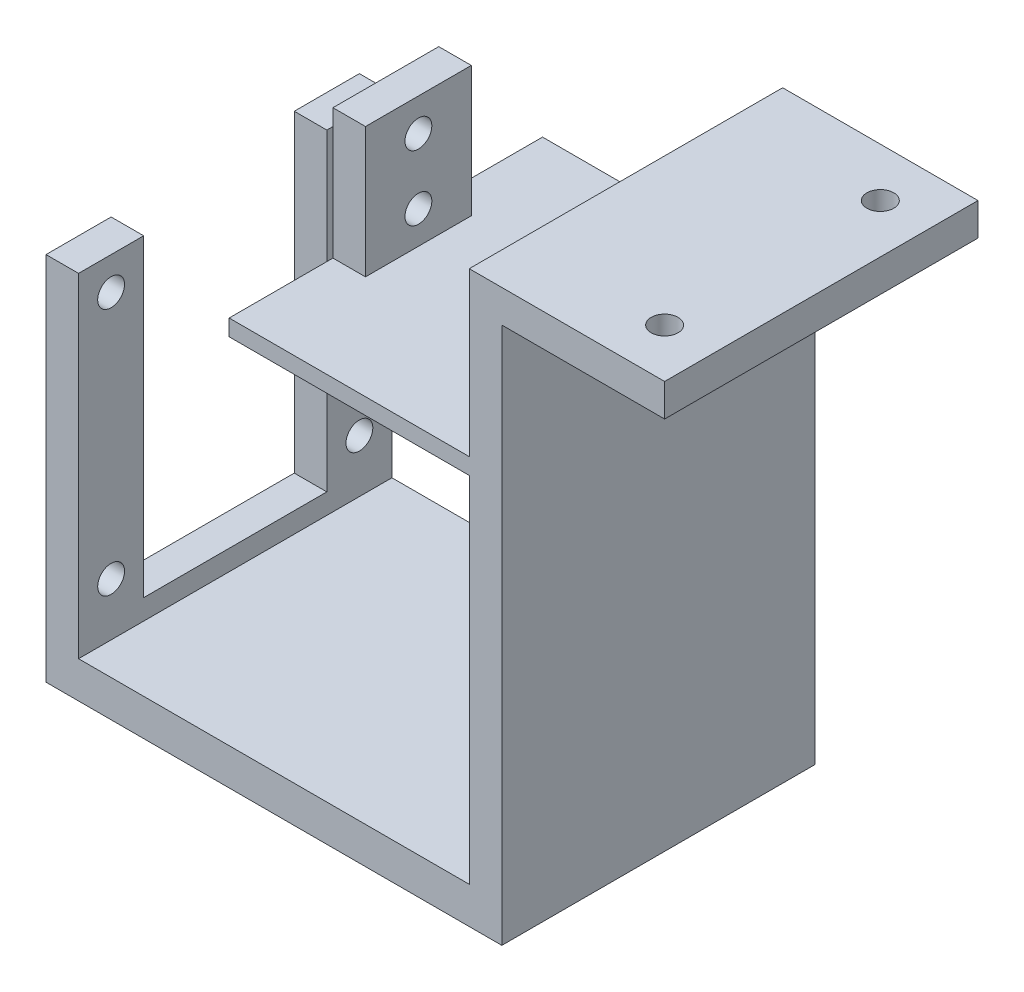
SolidWorks part; units mm, degrees
ref_plane "Front Plane" through (0, 0, 0) normal (0, 0, 1) x (1, 0, 0)
ref_plane "Top Plane" through (0, 0, 0) normal (0, 1, 0) x (1, 0, 0)
ref_plane "Right Plane" through (0, 0, 0) normal (1, 0, 0) x (0, 0, -1)
sketch "Sketch1" plane through (0, 0, 0) normal (1, 0, 0) x (0, 0, -1)
  line L1 (0, 0) -> (13, 0)
  line L2 (0, 0) -> (0, -16)
  line L3 (0, -16) -> (13, -16)
  line L4 (13, 0) -> (13, -16)
  dimension "D1" = 13
  dimension "D2" = 16
extrude "Boss-Extrude1" add sketch "Sketch1" along normal blind 4
sketch "Sketch2" plane through (4, 0, 0) normal (1, 0, 0) x (0, 0, -1)
  line L0 (13, 0) -> (0, 0) construction
  line L1 (0, -16) -> (13, -16) construction
  line L2 (13, -16) -> (13, 0) construction
  line L3 (0, 0) -> (0, -16) construction
  circle A0 centre (6.5, -4) radius 1.65
  circle A1 centre (6.5, -12) radius 1.65
  dimension "D1" = 3.3
  dimension "D2" = 3.3
  dimension "D3" = 4
  dimension "D4" = 4
  dimension "D5" = 6.5
  dimension "D6" = 6.5
extrude "Cut-Extrude1" cut sketch "Sketch2" against normal blind 10
sketch "Sketch3" plane through (0, -16, 0) normal (0, -1, 0) x (1, 0, 0)
  line L1 (4, 0) -> (0, 0)
  line L2 (4, 0) -> (4, -13)
  line L3 (4, -13) -> (0, -13)
  line L4 (0, 0) -> (0, -13)
extrude "Boss-Extrude2" add sketch "Sketch3" along normal blind 4
sketch "Sketch4" plane through (4, 0, 0) normal (1, 0, 0) x (0, 0, -1)
  line L0 (13, -20) -> (13, 0) construction
  line L1 (0, -20) -> (13, -20)
  line L2 (0, -20) -> (0, -16)
  line L3 (0, -16) -> (13, -16)
  line L4 (13, -20) -> (13, -16)
  dimension "D1" = 4
extrude "Boss-Extrude3" add sketch "Sketch4" along normal blind 60
sketch "Sketch6" plane through (0, -16, 0) normal (0, 1, 0) x (1, 0, 0)
  line L0 (64, 0) -> (4, 0) construction
  line L1 (64, 13) -> (60, 13)
  line L2 (64, 13) -> (64, -21)
  line L3 (64, -21) -> (60, -21)
  line L4 (60, 13) -> (60, -21)
  line L7 (64, 13) -> (60, 13)
  line L8 (64, 13) -> (64, 34)
  line L9 (64, 34) -> (60, 34)
  line L10 (60, 13) -> (60, 34)
  line M2 (4, 0) -> (64, 0)
  line M3 (64, 0) -> (64, 13)
  line M4 (64, 13) -> (4, 13)
  dimension "D1" = 4
  dimension "D2" = 21
  dimension "D3" = 21
extrude "Boss-Extrude4" add sketch "Sketch6" along normal blind 28 contours L4 L3 L2 M2 | L10 L8 L9 M4 | L4 M4 M2 M3 region at (62, -16, -6.5) region at (62, -16, -23.5) region at (62, -16, 10.5)
sketch "Sketch12" plane through (0, 0, -34) normal (0, 0, -1) x (-1, 0, 0)
  line L1 (-60, -16) -> (-64, -16)
  line L2 (-60, -16) -> (-60, 12)
  line L3 (-60, 12) -> (-64, 12)
  line L4 (-64, -16) -> (-64, 12)
extrude "Boss-Extrude8" add sketch "Sketch12" along normal blind 1.65
sketch "Sketch13" plane through (0, 0, 21) normal (0, 0, 1) x (1, 0, 0)
  line L1 (60, 12) -> (64, 12)
  line L2 (60, 12) -> (60, -16)
  line L3 (60, -16) -> (64, -16)
  line L4 (64, 12) -> (64, -16)
extrude "Boss-Extrude9" add sketch "Sketch13" along normal blind 1.65
sketch "Sketch14" plane through (0, 12, 0) normal (0, 1, 0) x (1, 0, 0)
  line L0 (64, 35.65) -> (64, -22.65) construction
  line L1 (64, 24.35) -> (60, 24.35)
  line L2 (64, 24.35) -> (64, -11.5284)
  line L3 (64, -11.5284) -> (60, -11.5284)
  line L4 (60, 24.35) -> (60, -11.5284)
  line L5 (60, 35.65) -> (60, -22.65) construction
  line L6 (64, -22.65) -> (60, -22.65) construction
  line L7 (60, 35.65) -> (64, 35.65) construction
  point P10 (62, -22.65)
  dimension "D1" = 11.3
  dimension "D2" = 11.3
extrude "Cut-Extrude5" cut sketch "Sketch14" against normal blind 24
sketch "Sketch15" plane through (64, 0, 0) normal (1, 0, 0) x (0, 0, -1)
  line L0 (-11.5284, 12) -> (-22.65, 12) construction
  line L1 (35.65, 12) -> (24.35, 12) construction
  line L2 (-22.65, -16) -> (-22.65, 12) construction
  line L3 (35.65, 12) -> (35.65, -16) construction
  circle A0 centre (-17, -11.5) radius 1.65
  circle A1 centre (30, -11.5) radius 1.65
  dimension "D1" = 3.3
  dimension "D2" = 3.3
  dimension "D3" = 23.5
  dimension "D4" = 23.5
  dimension "D5" = 5.65
  dimension "D6" = 5.65
extrude "Cut-Extrude6" cut sketch "Sketch15" against normal blind 24
sketch "Sketch16" plane through (0, 12, 0) normal (0, 1, 0) x (1, 0, 0)
  line L1 (60, -22.65) -> (64, -22.65)
  line L2 (60, -22.65) -> (60, -11.5284)
  line L3 (60, -11.5284) -> (64, -11.5284)
  line L4 (64, -22.65) -> (64, -11.5284)
  line L5 (60, 24.35) -> (64, 24.35)
  line L6 (60, 24.35) -> (60, 35.65)
  line L7 (60, 35.65) -> (64, 35.65)
  line L8 (64, 24.35) -> (64, 35.65)
extrude "Boss-Extrude10" add sketch "Sketch16" along normal blind 29.15
sketch "Sketch17" plane through (64, 0, 0) normal (1, 0, 0) x (0, 0, -1)
  line L0 (-22.65, -16) -> (-22.65, 41.15) construction
  line L1 (35.65, 41.15) -> (35.65, -16) construction
  line L2 (-22.65, 41.15) -> (-11.5284, 41.15) construction
  line L3 (24.35, 41.15) -> (35.65, 41.15) construction
  circle A0 centre (-17, 35.5) radius 1.65
  circle A1 centre (30, 35.5) radius 1.65
  dimension "D1" = 3.3
  dimension "D2" = 3.3
  dimension "D4" = 5.65
  dimension "D3" = 5.65
  dimension "D5" = 5.65
  dimension "D6" = 5.65
extrude "Cut-Extrude8" cut sketch "Sketch17" against normal blind 29.15
sketch "Sketch18" plane through (64, 0, 0) normal (1, 0, 0) x (0, 0, -1)
  line L1 (-22.65, -16) -> (13, -16)
  line L2 (-22.65, -16) -> (-22.65, -20)
  line L3 (-22.65, -20) -> (13, -20)
  line L4 (13, -16) -> (13, -20)
  line L5 (0, -20) -> (35.65, -20)
  line L6 (0, -20) -> (0, -16)
  line L7 (0, -16) -> (35.65, -16)
  line L8 (35.65, -20) -> (35.65, -16)
  line M9 (-22.65, -16) -> (0, -16)
  line M10 (0, -16) -> (0, -20)
  line M11 (0, -20) -> (13, -20)
  line M12 (13, -20) -> (13, -16)
  line M13 (13, -16) -> (35.65, -16)
extrude "Boss-Extrude11" add sketch "Sketch18" against normal blind 4 contours L2 L3 M10 M9 | L5 L8 M13 M12 | L1 M10 M11 M12 region at (64, -18, 11.325) region at (64, -18, -6.5) region at (64, -18, -24.325)
sketch "Sketch19" plane through (0, 0, -13) normal (0, 0, -1) x (-1, 0, 0)
  line L1 (0, -20) -> (-4, -20)
  line L2 (0, -20) -> (0, 0)
  line L3 (0, 0) -> (-4, 0)
  line L4 (-4, -20) -> (-4, 0)
extrude "Boss-Extrude12" add sketch "Sketch19" along normal blind 40
sketch "Sketch20" plane through (0, 0, 0) normal (-1, 0, 0) x (0, 0, 1)
  line L0 (-53, 0) -> (0, 0) construction
  line L1 (-53, -20) -> (-53, 0) construction
  circle A0 centre (-46.5, -4) radius 1.65
  circle A1 centre (-46.5, -12) radius 1.65
  dimension "D1" = 3.3
  dimension "D2" = 3.3
  dimension "D3" = 4
  dimension "D4" = 8
  dimension "D5" = 6.5
  dimension "D6" = 6.5
extrude "Cut-Extrude9" cut sketch "Sketch20" against normal blind 40
sketch "Sketch21" plane through (0, -16, 0) normal (0, 1, 0) x (1, 0, 0)
  line L0 (4, 53) -> (4, 13) construction
  line L1 (28, 21.75) -> (24, 21.75)
  line L2 (28, 21.75) -> (28, -8.75)
  line L3 (28, -8.75) -> (24, -8.75)
  line L4 (24, 21.75) -> (24, -8.75)
  line L5 (60, 13) -> (4, 13) construction
  line L6 (60, 0) -> (4, 0) construction
  dimension "D1" = 20
  dimension "D2" = 4
  dimension "D3" = 8.75
  dimension "D4" = 8.75
extrude "Boss-Extrude13" add sketch "Sketch21" along normal blind 38.5
sketch "Sketch23" plane through (0, 22.5, 0) normal (0, 1, 0) x (1, 0, 0)
  line L1 (24, 21.75) -> (28, 21.75)
  line L2 (24, 21.75) -> (24, 25.75)
  line L3 (24, 25.75) -> (28, 25.75)
  line L4 (28, 21.75) -> (28, 25.75)
  line L6 (24, 21.75) -> (24, -8.75) construction
  line L7 (28, -8.75) -> (28, 21.75) construction
  line L8 (24, -8.75) -> (28, -8.75)
  line L9 (24, -8.75) -> (24, -12.75)
  line L10 (24, -12.75) -> (28, -12.75)
  line L11 (28, -8.75) -> (28, -12.75)
  dimension "D1" = 4
  dimension "D2" = 4
  dimension "D3" = 4
  dimension "D4" = 0
extrude "Boss-Extrude14" add sketch "Sketch23" against normal blind 38.5
sketch "Sketch24" plane through (0, 22.5, 0) normal (0, 1, 0) x (1, 0, 0)
  line L1 (28, 25.75) -> (24, 25.75)
  line L2 (28, 25.75) -> (28, -12.75)
  line L3 (28, -12.75) -> (24, -12.75)
  line L4 (24, 25.75) -> (24, -12.75)
extrude "Boss-Extrude15" add sketch "Sketch24" along normal blind 3
sketch "Sketch25" plane through (28, 0, 0) normal (1, 0, 0) x (0, 0, -1)
  line L0 (25.75, -16) -> (25.75, 25.5) construction
  line L1 (25.75, -13) -> (-12.75, -13)
  line L2 (25.75, -13) -> (25.75, -20)
  line L3 (25.75, -20) -> (-12.75, -20)
  line L4 (-12.75, -13) -> (-12.75, -20)
  line L5 (13, -16) -> (25.75, -16) construction
  line L6 (-12.75, -16) -> (0, -16) construction
  line L7 (-12.75, -16) -> (-12.75, 25.5) construction
  dimension "D1" = 3
  dimension "D2" = 4
  dimension "D3" = 0
sketch "Sketch27" plane through (0, -20, 0) normal (0, -1, 0) x (1, 0, 0)
  line L1 (64, 22.65) -> (60, 22.65)
  line L2 (64, 22.65) -> (64, -35.65)
  line L3 (64, -35.65) -> (60, -35.65)
  line L4 (60, 22.65) -> (60, -35.65)
extrude "Cut-Extrude10" cut sketch "Sketch27" against normal blind 100
sketch "Sketch29" plane through (28, 0, 0) normal (1, 0, 0) x (0, 0, -1)
  line L2 (-12.75, -13) -> (25.75, -13)
  line L3 (-12.75, -13) -> (-12.75, -20)
  line L4 (-12.75, -20) -> (25.75, -20)
  line L5 (25.75, -13) -> (25.75, -20)
extrude "Boss-Extrude16" add sketch "Sketch29" along normal blind 40 and the other way blind 28
sketch "Sketch30" plane through (24, 0, 0) normal (-1, 0, 0) x (0, 0, 1)
  line L0 (12.75, -13) -> (12.75, 25.5) construction
  line L1 (-25.75, 25.5) -> (12.75, 25.5) construction
  line L2 (-25.75, -13) -> (12.75, -13) construction
  line L3 (-25.75, -13) -> (-25.75, 25.5) construction
  circle A0 centre (8.75, 21.5) radius 1.65
  circle A1 centre (8.75, -9) radius 1.65
  circle A2 centre (-21.75, 21.5) radius 1.65
  circle A3 centre (-21.75, -9) radius 1.65
  dimension "D1" = 3.3
  dimension "D4" = 3.3
  dimension "D7" = 3.3
  dimension "D12" = 3.3
  dimension "D2" = 4
  dimension "D3" = 4
  dimension "D5" = 4
  dimension "D6" = 4
  dimension "D8" = 4
  dimension "D9" = 4
  dimension "D10" = 4
  dimension "D11" = 4
extrude "Cut-Extrude11" cut sketch "Sketch30" against normal blind 40
sketch "Sketch31" plane through (0, 25.5, 0) normal (0, 1, 0) x (1, 0, 0)
  line L0 (28, -12.75) -> (28, 25.75) construction
  line L1 (28, 17.75) -> (24, 17.75)
  line L2 (28, 17.75) -> (28, -4.75)
  line L3 (28, -4.75) -> (24, -4.75)
  line L4 (24, 17.75) -> (24, -4.75)
  line L5 (24, 25.75) -> (24, -12.75) construction
  line L6 (24, -12.75) -> (28, -12.75) construction
  dimension "D1" = 8
  dimension "D2" = 8
extrude "Cut-Extrude12" cut sketch "Sketch31" against normal blind 38.5
sketch "Sketch32" plane through (68, 0, 0) normal (1, 0, 0) x (0, 0, -1)
  line L0 (25.75, -20) -> (25.75, -13) construction
  line L1 (-12.75, -13) -> (25.75, -13)
  line L2 (-12.75, -13) -> (-12.75, -15.5)
  line L3 (-12.75, -15.5) -> (25.75, -15.5)
  line L4 (25.75, -13) -> (25.75, -15.5)
  dimension "D1" = 2.5
extrude "Cut-Extrude13" cut sketch "Sketch32" against normal blind 40
sketch "Sketch33" plane through (0, 25.5, 0) normal (0, 1, 0) x (1, 0, 0)
  line L1 (24, -12.75) -> (28, -12.75)
  line L2 (24, -12.75) -> (24, -4.75)
  line L3 (24, -4.75) -> (28, -4.75)
  line L4 (28, -12.75) -> (28, -4.75)
  line L5 (24, 17.75) -> (28, 17.75)
  line L6 (24, 17.75) -> (24, 25.75)
  line L7 (24, 25.75) -> (28, 25.75)
  line L8 (28, 17.75) -> (28, 25.75)
extrude "Boss-Extrude17" add sketch "Sketch33" against normal blind 8
sketch "Sketch34" plane through (28, 0, 0) normal (1, 0, 0) x (0, 0, -1)
  line L0 (-12.75, 25.5) -> (-4.75, 25.5) construction
  line L1 (-12.75, -15.5) -> (-12.75, 25.5) construction
  line L2 (25.75, -15.5) -> (25.75, 25.5) construction
  line L3 (17.75, 25.5) -> (25.75, 25.5) construction
  circle A0 centre (-8.75, 21.5) radius 1.65
  circle A1 centre (21.75, 21.5) radius 1.65
  dimension "D1" = 3.3
  dimension "D2" = 3.3
  dimension "D3" = 4
  dimension "D4" = 4
  dimension "D5" = 4
  dimension "D6" = 4
extrude "Cut-Extrude14" cut sketch "Sketch34" against normal blind 8
sketch "Sketch35" plane through (0, -13, 0) normal (0, 1, 0) x (1, 0, 0)
  line L0 (0, -12.75) -> (24, -12.75) construction
  line L1 (10, -12.75) -> (14, -12.75)
  line L2 (10, -12.75) -> (10, 30.75)
  line L3 (10, 30.75) -> (14, 30.75)
  line L4 (14, -12.75) -> (14, 30.75)
  line L5 (24, 25.75) -> (24, 17.75) construction
  line L6 (4, 25.75) -> (24, 25.75) construction
  dimension "D1" = 10
  dimension "D2" = 4
  dimension "D3" = 5
extrude "Boss-Extrude18" add sketch "Sketch35" along normal blind 13
sketch "Sketch36" plane through (0, -20, 0) normal (0, -1, 0) x (1, 0, 0)
  line L1 (0, 12.75) -> (68, 12.75) construction
  line L2 (0, 12.75) -> (10, 12.75)
  line L3 (0, 12.75) -> (0, -67.25)
  line L4 (0, -67.25) -> (10, -67.25)
  line L5 (10, 12.75) -> (10, -67.25)
  line L6 (4, -53) -> (4, -25.75) construction
  dimension "D1" = 10
  dimension "D2" = 80
  dimension "D3" = 4
extrude "Cut-Extrude15" cut sketch "Sketch36" against normal up to vertex (45.5 mm away) up to point (24, 25.5, -25.75)
sketch "Sketch37" plane through (10, 0, 0) normal (-1, 0, 0) x (0, 0, 1)
  line L1 (-30.75, -13) -> (-25.75, -13)
  line L2 (-30.75, -13) -> (-30.75, -20)
  line L3 (-30.75, -20) -> (-25.75, -20)
  line L4 (-25.75, -13) -> (-25.75, -20)
extrude "Boss-Extrude19" add sketch "Sketch37" against normal blind 4
sketch "Sketch41" plane through (14, 0, 0) normal (1, 0, 0) x (0, 0, -1)
  line L1 (25.75, -20) -> (38.75, -20)
  line L2 (25.75, -20) -> (25.75, 0)
  line L3 (25.75, 0) -> (38.75, 0)
  line L4 (38.75, -20) -> (38.75, 0)
  dimension "D1" = 13
  dimension "D2" = 20
extrude "Boss-Extrude20" add sketch "Sketch41" against normal blind 4
sketch "Sketch42" plane through (10, 0, 0) normal (-1, 0, 0) x (0, 0, 1)
  line L0 (-38.75, 0) -> (12.75, 0) construction
  line L1 (-38.75, -20) -> (-38.75, 0) construction
  circle A0 centre (-32.25, -4) radius 1.65
  circle A1 centre (-32.25, -12) radius 1.65
  dimension "D1" = 3.3
  dimension "D2" = 3.3
  dimension "D3" = 4
  dimension "D4" = 6.5
  dimension "D5" = 8
  dimension "D6" = 6.5
extrude "Cut-Extrude18" cut sketch "Sketch42" against normal blind 4
sketch "Sketch43" plane through (0, 0, 0) normal (0, 1, 0) x (1, 0, 0)
  line L0 (10, 38.75) -> (10, -12.75) construction
  line L1 (14, -12.75) -> (10, -12.75)
  line L2 (14, -12.75) -> (14, 25.75)
  line L3 (14, 25.75) -> (10, 25.75)
  line L4 (10, -12.75) -> (10, 25.75)
  line L5 (10, 38.75) -> (14, 38.75) construction
  dimension "D1" = 13
extrude "Cut-Extrude19" cut sketch "Sketch43" against normal blind 10
sketch "Sketch44" plane through (28, 0, 0) normal (1, 0, 0) x (0, 0, -1)
  line L0 (-4.75, -13) -> (-4.75, 25.5) construction
  line L1 (-12.75, -15.5) -> (-4.75, -15.5)
  line L2 (-12.75, -15.5) -> (-12.75, -6.5)
  line L3 (-12.75, -6.5) -> (-4.75, -6.5)
  line L4 (-4.75, -15.5) -> (-4.75, -6.5)
  line L5 (17.75, -13) -> (17.75, 25.5) construction
  line L6 (25.75, -15.5) -> (17.75, -15.5)
  line L7 (25.75, -15.5) -> (25.75, -6.5)
  line L8 (25.75, -6.5) -> (17.75, -6.5)
  line L9 (17.75, -15.5) -> (17.75, -6.5)
  dimension "D1" = 9
  dimension "D2" = 9
extrude "Boss-Extrude21" add sketch "Sketch44" against normal blind 4
sketch "Sketch45" plane through (24, 0, 0) normal (-1, 0, 0) x (0, 0, 1)
  line L0 (4.75, -13) -> (12.75, -13) construction
  line L1 (-25.75, -13) -> (-17.75, -13) construction
  line L2 (-25.75, -13) -> (-25.75, 25.5) construction
  line L3 (12.75, -13) -> (12.75, 25.5) construction
  circle A0 centre (-21.75, -7) radius 1.65
  circle A1 centre (8.75, -7) radius 1.65
  dimension "D1" = 3.3
  dimension "D2" = 3.3
  dimension "D3" = 6
  dimension "D4" = 6
  dimension "D5" = 4
  dimension "D6" = 4
extrude "Cut-Extrude20" cut sketch "Sketch45" against normal blind 4
sketch "Sketch46" plane through (0, -15.5, 0) normal (0, 1, 0) x (1, 0, 0)
  line L0 (68, -12.75) -> (68, 25.75) construction
  line L1 (64, 18.2859) -> (67, 20.0179)
  line L2 (67, 20.0179) -> (67, 23.4821)
  line L3 (67, 23.4821) -> (64, 25.2141)
  line L4 (64, 25.2141) -> (61, 23.4821)
  line L5 (61, 23.4821) -> (61, 20.0179)
  line L6 (61, 20.0179) -> (64, 18.2859)
  line L7 (64, -12.2141) -> (67, -10.4821)
  line L8 (67, -10.4821) -> (67, -7.0179)
  line L9 (67, -7.0179) -> (64, -5.2859)
  line L10 (64, -5.2859) -> (61, -7.0179)
  line L11 (61, -7.0179) -> (61, -10.4821)
  line L12 (61, -10.4821) -> (64, -12.2141)
  line L13 (28, 25.75) -> (68, 25.75) construction
  line L14 (28, -12.75) -> (68, -12.75) construction
  circle A0 centre (64, 21.75) radius 3 construction
  circle A1 centre (64, -8.75) radius 3 construction
  dimension "D3" = 6
  dimension "D7" = 6
  dimension "D1" = 4
  dimension "D2" = 4
  dimension "D4" = 1
  dimension "D5" = 4
  dimension "D6" = 4
  dimension "D8" = 1
extrude "Cut-Extrude21" cut sketch "Sketch46" against normal blind 3
sketch "Sketch49" plane through (0, -15.5, 0) normal (0, 1, 0) x (1, 0, 0)
  line L0 (68, -12.75) -> (68, 25.75) construction
  line L1 (28, 25.75) -> (68, 25.75) construction
  line L2 (28, -12.75) -> (68, -12.75) construction
  circle A0 centre (64, 21.75) radius 1.65
  circle A1 centre (64, -8.75) radius 1.65
  dimension "D1" = 3.3
  dimension "D2" = 3.3
  dimension "D3" = 4
  dimension "D4" = 4
  dimension "D5" = 4
  dimension "D6" = 4
extrude "Cut-Extrude22" cut sketch "Sketch49" against normal blind 5
ref_plane "Plane1" through (10, -10, -25.75) normal (0, 0, 1) x (1, 0, 0)
sketch "Sketch54" plane through (0, -10, 0) normal (0, 1, 0) x (1, 0, 0)
  line L0 (10, -12.75) -> (14, -12.75) construction
  line L1 (10, 25.75) -> (11, 25.75)
  line L2 (10, 25.75) -> (10, -12.75)
  line L3 (10, -12.75) -> (11, -12.75)
  line L4 (11, 25.75) -> (11, -12.75)
  dimension "D1" = 1
  dimension "D2" = 0
extrude "Cut-Extrude24" cut sketch "Sketch54" against normal blind 50
sketch "Sketch55" plane through (24, 0, 0) normal (-1, 0, 0) x (0, 0, 1)
  line L0 (4.75, -13) -> (4.75, 25.5) construction
  line L1 (12.75, -13) -> (4.75, -13)
  line L2 (12.75, -13) -> (12.75, -3)
  line L3 (12.75, -3) -> (4.75, -3)
  line L4 (4.75, -13) -> (4.75, -3)
  line L5 (-25.75, -13) -> (-25.75, 25.5) construction
  line L6 (-17.75, -13) -> (-25.75, -13)
  line L7 (-17.75, -13) -> (-17.75, -3)
  line L8 (-17.75, -3) -> (-25.75, -3)
  line L9 (-25.75, -13) -> (-25.75, -3)
  dimension "D1" = 10
  dimension "D2" = 10
extrude "Boss-Extrude22" add sketch "Sketch55" against normal blind 4
sketch "Sketch56" plane through (24, 0, 0) normal (-1, 0, 0) x (0, 0, 1)
  line L0 (-17.75, -13) -> (-17.75, 25.5) construction
  line L1 (4.75, -13) -> (4.75, 25.5) construction
  circle A0 centre (-21.75, -9) radius 1.65
  circle A1 centre (8.75, -9) radius 1.65
  circle A2 centre (-21.75, 21.5) radius 1.65 construction
  circle A3 centre (8.75, 21.5) radius 1.65 construction
  dimension "D3" = 3.3
  dimension "D4" = 3.3
  dimension "D1" = 30.5
  dimension "D2" = 30.5
  dimension "D5" = 4
  dimension "D6" = 4
extrude "Cut-Extrude25" cut sketch "Sketch56" against normal blind 4
sketch "Sketch57" plane through (0, -13, 0) normal (0, 1, 0) x (1, 0, 0)
  line L1 (24, -12.75) -> (-1, -12.75)
  line L2 (24, -12.75) -> (24, 57.25)
  line L3 (24, 57.25) -> (-1, 57.25)
  line L4 (-1, -12.75) -> (-1, 57.25)
  dimension "D1" = 70
  dimension "D2" = 25
extrude "Cut-Extrude26" cut sketch "Sketch57" against normal blind 10 and the other way blind 15
sketch "Sketch58" plane through (0, -20, 0) normal (0, -1, 0) x (1, 0, 0)
  line L0 (28, -25.75) -> (28, 12.75) construction
  line L1 (28, -25.75) -> (75.5, -25.75)
  line L2 (28, -25.75) -> (28, 12.75)
  line L3 (28, 12.75) -> (75.5, 12.75)
  line L4 (75.5, -25.75) -> (75.5, 12.75)
  line L5 (24, -25.75) -> (68, -25.75) construction
  dimension "D1" = 38.5
  dimension "D2" = 47.5
extrude "Boss-Extrude24" add sketch "Sketch58" against normal blind 4.5
sketch "Sketch59" plane through (0, -20, 0) normal (0, -1, 0) x (1, 0, 0)
  line L0 (24, -25.75) -> (75.5, -25.75) construction
  line L1 (75.5, 12.75) -> (76, 12.75)
  line L2 (75.5, 12.75) -> (75.5, -25.75)
  line L3 (75.5, -25.75) -> (76, -25.75)
  line L4 (76, 12.75) -> (76, -25.75)
  dimension "D1" = 0
  dimension "D2" = 0.5
extrude "Boss-Extrude25" add sketch "Sketch59" against normal blind 4.5
sketch "Sketch60" plane through (0, -20, 0) normal (0, -1, 0) x (1, 0, 0)
  line L0 (24, -25.75) -> (76, -25.75) construction
  line L1 (76, 12.75) -> (80, 12.75)
  line L2 (76, 12.75) -> (76, -25.75)
  line L3 (76, -25.75) -> (80, -25.75)
  line L4 (80, 12.75) -> (80, -25.75)
  dimension "D1" = 0
  dimension "D2" = 4
extrude "Boss-Extrude26" add sketch "Sketch60" against normal blind 69.5
sketch "Sketch61" plane through (80, 0, 0) normal (1, 0, 0) x (0, 0, -1)
  line L0 (-12.75, 49.5) -> (-12.75, -20) construction
  line L1 (25.75, 49.5) -> (-12.75, 49.5)
  line L2 (25.75, 49.5) -> (25.75, 47.0423)
  line L3 (25.75, 47.0423) -> (-12.75, 47.0423)
  line L4 (-12.75, 49.5) -> (-12.75, 47.0423)
extrude "Boss-Extrude27" add sketch "Sketch61" along normal blind 20
sketch "Sketch62" plane through (76, 0, 0) normal (-1, 0, 0) x (0, 0, 1)
  line L0 (12.75, 49.5) -> (12.75, -15.5) construction
  line L1 (12.75, 28) -> (-25.75, 28)
  line L2 (12.75, 28) -> (12.75, 30)
  line L3 (12.75, 30) -> (-25.75, 30)
  line L4 (-25.75, 28) -> (-25.75, 30)
  line L5 (-25.75, 49.5) -> (-25.75, -15.5) construction
  line L6 (-25.75, -15.5) -> (12.75, -15.5) construction
  dimension "D1" = 43.5
  dimension "D2" = 2
extrude "Boss-Extrude31" add sketch "Sketch62" along normal blind 29.5
sketch "Sketch64" plane through (0, 30, 0) normal (0, 1, 0) x (1, 0, 0)
  line L0 (46.5, -12.75) -> (46.5, 25.75) construction
  line L1 (46.5, 0) -> (50.5, 0)
  line L2 (46.5, 0) -> (46.5, 13)
  line L3 (46.5, 13) -> (50.5, 13)
  line L4 (50.5, 0) -> (50.5, 13)
  line L5 (46.5, -12.75) -> (76, -12.75) construction
  dimension "D1" = 12.75
  dimension "D2" = 13
  dimension "D3" = 4
extrude "Boss-Extrude32" add sketch "Sketch64" along normal blind 16
sketch "Sketch65" plane through (46.5, 0, 0) normal (-1, 0, 0) x (0, 0, 1)
  line L0 (-13, 46) -> (0, 46) construction
  line L1 (-13, 46) -> (-13, 30) construction
  line L2 (0, 46) -> (0, 30) construction
  circle A0 centre (-6.5, 34) radius 1.65
  circle A1 centre (-6.5, 42) radius 1.65
  dimension "D3" = 3.3
  dimension "D6" = 3.3
  dimension "D1" = 4
  dimension "D2" = 6.5
  dimension "D4" = 6.5
  dimension "D5" = 8
extrude "Cut-Extrude27" cut sketch "Sketch65" against normal blind 16
sketch "Sketch66" plane through (0, 0, -25.75) normal (0, 0, -1) x (-1, 0, 0)
  line L1 (-76, 49.5) -> (-100, 49.5)
  line L2 (-76, 49.5) -> (-76, 50)
  line L3 (-76, 50) -> (-100, 50)
  line L4 (-100, 49.5) -> (-100, 50)
  dimension "D1" = 0.5
extrude "Boss-Extrude33" add sketch "Sketch66" against normal blind 38.5
sketch "Sketch67" plane through (0, 47.0423, 0) normal (0, -1, 0) x (1, 0, 0)
  line L1 (80, -25.75) -> (100, -25.75)
  line L2 (80, -25.75) -> (80, 12.75)
  line L3 (80, 12.75) -> (100, 12.75)
  line L4 (100, -25.75) -> (100, 12.75)
sketch "Sketch69" plane through (0, 47.0423, 0) normal (0, -1, 0) x (1, 0, 0)
  line L1 (80, -25.75) -> (100, -25.75)
  line L2 (80, -25.75) -> (80, 12.75)
  line L3 (80, 12.75) -> (100, 12.75)
  line L4 (100, -25.75) -> (100, 12.75)
extrude "Boss-Extrude34" add sketch "Sketch69" along normal blind 1.04
sketch "Sketch70" plane through (0, 46.0023, 0) normal (0, -1, 0) x (1, 0, 0)
  line L0 (100, -25.75) -> (100, 12.75) construction
  line L1 (80, 12.75) -> (100, 12.75) construction
  line L2 (80, -25.75) -> (100, -25.75) construction
  circle A0 centre (94, 6.75) radius 1.65
  circle A1 centre (94, -19.75) radius 1.65
  dimension "D5" = 3.3
  dimension "D6" = 3.3
  dimension "D1" = 6
  dimension "D2" = 6
  dimension "D3" = 6
  dimension "D4" = 6
extrude "Cut-Extrude29" cut sketch "Sketch70" against normal blind 10
